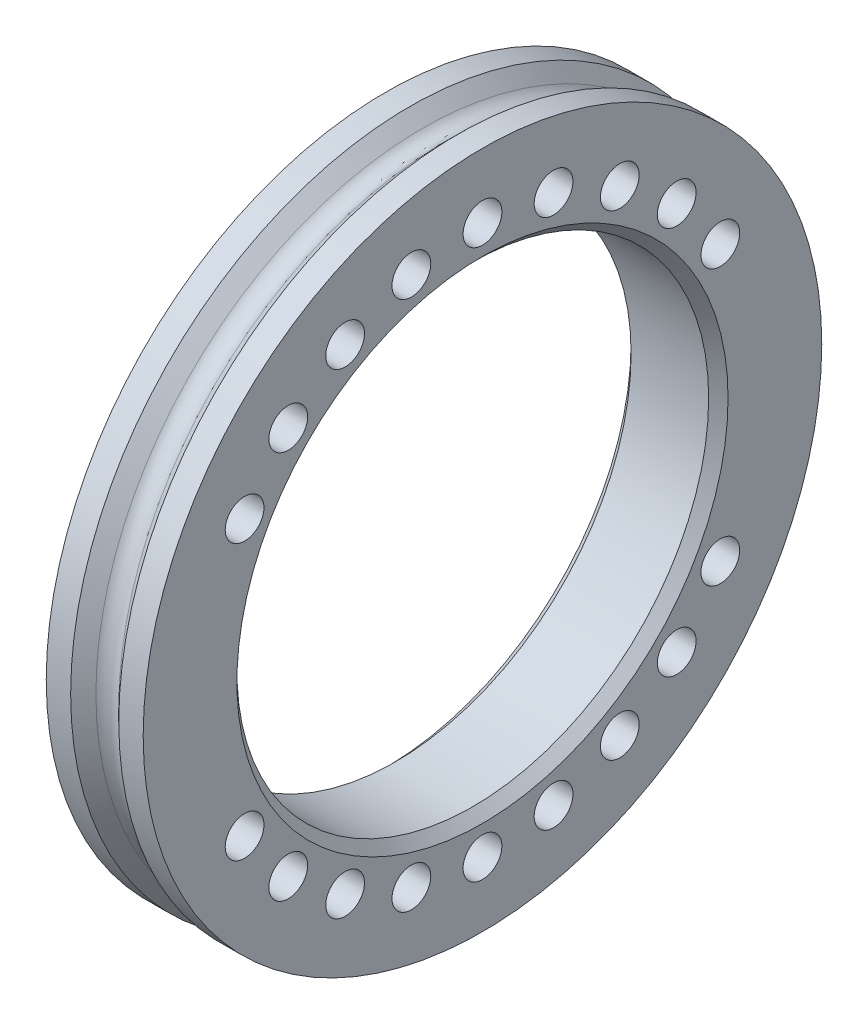
SolidWorks part; units mm, degrees
ref_plane "Front Plane" through (0, 0, 0) normal (0, 0, 1) x (1, 0, 0)
ref_plane "Top Plane" through (0, 0, 0) normal (0, 1, 0) x (1, 0, 0)
ref_plane "Right Plane" through (0, 0, 0) normal (1, 0, 0) x (0, 0, -1)
sketch "Sketch1" plane through (0, 0, 0) normal (0, 0, 1) x (1, 0, 0)
  line L0 (0, 0) -> (0, 124.5) construction
  line L1 (0, 115.9424) -> (9.1924, 106.75)
  line L2 (15, 140.5) -> (-15, 140.5) construction
  line L3 (15, 140.5) -> (15, 108.5) construction
  line L4 (15, 108.5) -> (-15, 108.5) construction
  line L5 (-15, 140.5) -> (-15, 108.5) construction
  line L6 (15, 140.5) -> (-15, 108.5) construction
  line L7 (15, 108.5) -> (-15, 140.5) construction
  line L8 (15, 105) -> (-15, 105)
  line L9 (15, 105) -> (15, 73)
  line L10 (15, 73) -> (-15, 73)
  line L11 (-15, 105) -> (-15, 73)
  line L12 (15, 105) -> (-15, 73) construction
  line L13 (15, 73) -> (-15, 105) construction
  line L14 (0, 115.9424) -> (-9.1924, 106.75)
  line L15 (9.1924, 106.75) -> (0, 97.5576)
  line L16 (-9.1924, 106.75) -> (0, 97.5576)
  line L17 (0, 115.9424) -> (0, 97.5576) construction
  line L18 (9.1924, 106.75) -> (-9.1924, 106.75) construction
  line L19 (0, 0) -> (135.8124, 0) construction
  point P7 (0, 89)
  point P13 (0, 106.75)
  dimension "D2" = 140.5
  dimension "D1" = 30
  dimension "D3" = 73
  dimension "D4" = 32
  dimension "D5" = 1.75
  dimension "D6" = 13
revolve "Revolve1" add sketch "Sketch1" angle 360 about L19 region at (0, 88.1722, 0)
chamfer "Chamfer1" distance 3 angle 45 2 edges at (15, 0, 73) (-15, 0, 73)
ref_axis "Axis2" through (12, 0, 0) along (-1, 0, 0)
fillet "Fillet3" radius 5 1 edges at (0, 0, 97.5576)
sketch "Sketch3" plane through (15, 0, 0) normal (1, 0, 0) x (0, 0, -1)
  circle A0 centre (0, 0) radius 85 construction
  circle A1 centre (0, 85) radius 6
  dimension "D1" = 170
  dimension "D2" = 12
extrude "Cut-Extrude3" cut sketch "Sketch3" against normal through all
pattern_circular "CirPattern2" count 5 every 15 about axis through (12, 0, 0) along (-1, 0, 0) of "Cut-Extrude3" other way count 5
mirror "Mirror1" about plane through (0, 0, 0) normal (0, 1, 0) of "CirPattern2"
